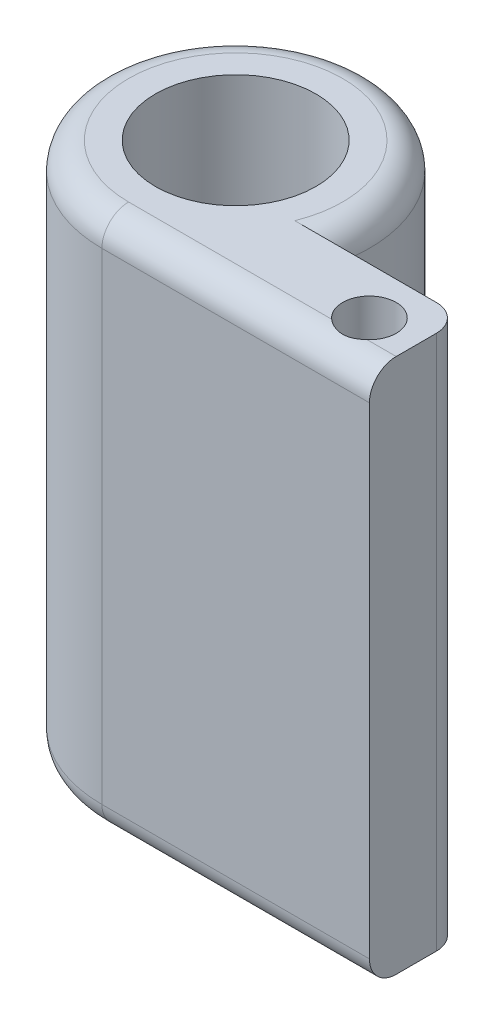
SolidWorks part; units mm, degrees
ref_plane "Front Plane" through (0, 0, 0) normal (0, 0, 1) x (1, 0, 0)
ref_plane "Top Plane" through (0, 0, 0) normal (0, 1, 0) x (1, 0, 0)
ref_plane "Right Plane" through (0, 0, 0) normal (1, 0, 0) x (0, 0, -1)
sketch "Sketch1" plane through (0, 0, 0) normal (0, 1, 0) x (1, 0, 0)
  circle A0 centre (0, 0) radius 12.7
extrude "Boss-Extrude1" add sketch "Sketch1" along normal blind 50.8
sketch "Sketch2" plane through (0, 50.8, 0) normal (0, 1, 0) x (1, 0, 0)
  circle A0 centre (0, 0) radius 7.62
sketch "Sketch3" plane through (0, 50.8, 0) normal (0, 1, 0) x (1, 0, 0)
  line L0 (0, 0) -> (0, -12.7)
  circle A0 centre (0, 0) radius 12.7 construction
  point P6 (0, 0)
sketch "Sketch4" plane through (0, 0, 0) normal (1, 0, 0) x (0, 0, -1)
  line L0 (-12.7, 50.8) -> (-12.7, 0) construction
  line L1 (-12.7, 50.8) -> (-3.81, 50.8)
  line L2 (-12.7, 50.8) -> (-12.7, 0)
  line L3 (-12.7, 0) -> (-3.81, 0)
  line L4 (-3.81, 50.8) -> (-3.81, 0)
  line L5 (-12.7, 50.8) -> (-3.81, 0) construction
  line L6 (-12.7, 0) -> (-3.81, 50.8) construction
  line L7 (-12.7, 50.8) -> (-12.7, 0) construction
  point P0 (-8.255, 25.4)
  point P5 (-19.7144, 7.7705)
  point P6 (-3.6991, 44.4438)
  point P7 (-12.7, 50.8)
  point P9 (-12.7, 8.8968)
  point P12 (-12.7, 0)
  point P15 (-12.7, 50.8)
  point P16 (0, 0)
sketch "Sketch5" plane through (0, 0, 0) normal (0, -1, 0) x (-1, 0, 0)
  line L0 (0, 0) -> (0, -12.7)
  circle A0 centre (0, 0) radius 12.7 construction
extrude "Boss-Extrude3" add sketch "Sketch4" along normal blind 25.4
sketch "Sketch7" plane through (0, 50.8, 0) normal (0, 1, 0) x (1, 0, 0)
  line L0 (25.4, -3.81) -> (16.51, -12.7)
  line L1 (25.4, -12.7) -> (0, -12.7) construction
  circle A0 centre (20.955, -8.255) radius 2.54
extrude "Cut-Extrude1" cut sketch "Sketch7" against normal through all contours L0 A0 | L0 A0 region at (21.7173, 50.8, 9.0173) region at (20.1927, 50.8, 7.4927)
fillet "Fillet3" radius 2.54 4 edges at (12.7, 0, 12.7) (12.7, 50.8, 12.7) (-7.5134, 0, -10.2391) (-7.5134, 50.8, -10.2391)
extrude "Cut-Extrude2" cut sketch "Sketch2" against normal through all contours A0
fillet "Fillet4" radius 2.54 1 edges at (25.4, 25.4, 3.81)
